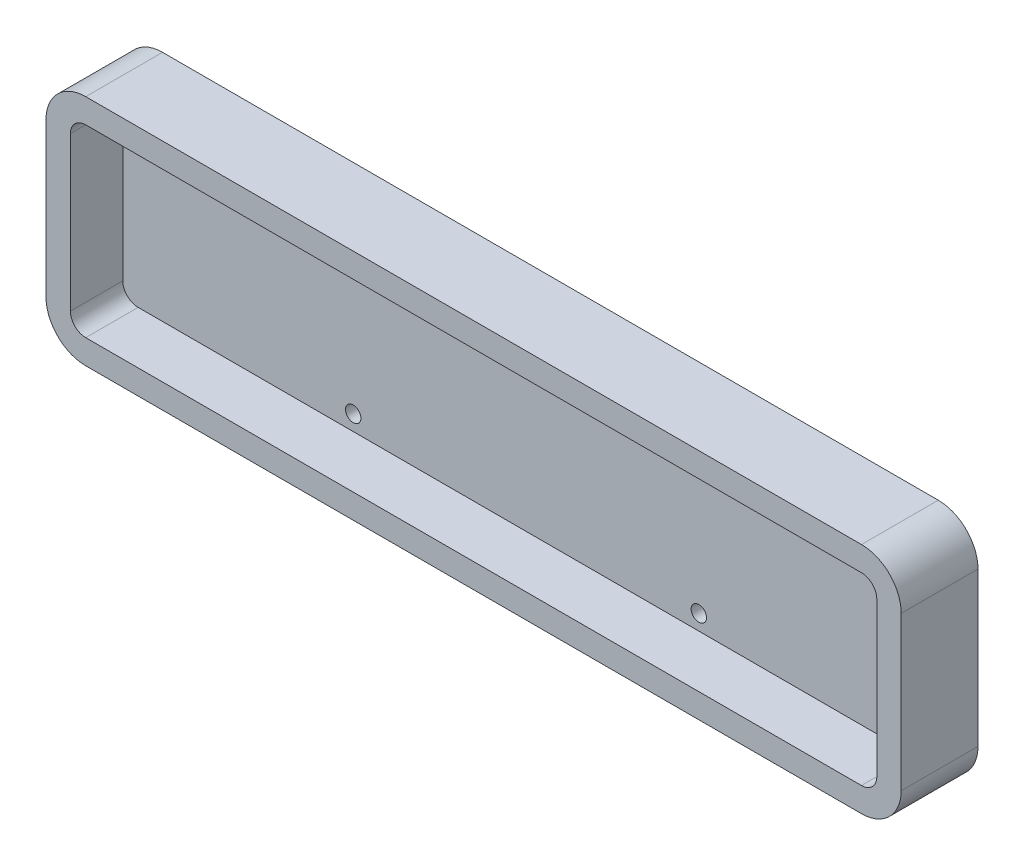
SolidWorks part; units mm, degrees
material "6061-T6 (SS)"
ref_plane "Front Plane" through (0, 0, 0) normal (0, 0, 1) x (1, 0, 0)
ref_plane "Top Plane" through (0, 0, 0) normal (0, 1, 0) x (1, 0, 0)
ref_plane "Right Plane" through (0, 0, 0) normal (1, 0, 0) x (0, 0, -1)
sketch "Sketch1" plane through (0, 0, 0) normal (0, 0, 1) x (1, 0, 0)
  line L0 (-50.5, 15.175) -> (50.5, 15.175)
  line L1 (-50.5, -12) -> (50.5, -12)
  line L2 (-52.5, -10) -> (-52.5, 10)
  line L3 (-50.5, 12) -> (50.5, 12)
  line L4 (52.5, -10) -> (52.5, 10)
  line L5 (-52.5, -12) -> (52.5, 12) construction
  line L6 (-52.5, 12) -> (52.5, -12) construction
  line L7 (55.675, -10) -> (55.675, 10)
  line L8 (-50.5, -15.175) -> (50.5, -15.175)
  line L9 (-55.675, -10) -> (-55.675, 10)
  arc A0 (-52.5, -10) -> (-50.5, -12) centre (-50.5, -10) ccw
  arc A1 (50.5, -12) -> (52.5, -10) centre (50.5, -10) ccw
  arc A2 (52.5, 10) -> (50.5, 12) centre (50.5, 10) ccw
  arc A3 (-50.5, 12) -> (-52.5, 10) centre (-50.5, 10) ccw
  arc A4 (55.675, 10) -> (50.5, 15.175) centre (50.5, 10) ccw
  arc A5 (50.5, -15.175) -> (55.675, -10) centre (50.5, -10) ccw
  arc A6 (-55.675, -10) -> (-50.5, -15.175) centre (-50.5, -10) ccw
  arc A7 (-50.5, 15.175) -> (-55.675, 10) centre (-50.5, 10) ccw
  point P0 (0, 0)
  dimension "D3" = 2
  dimension "D1" = 105
  dimension "D2" = 24
  dimension "D4" = 3.175
extrude "Boss-Extrude1" add sketch "Sketch1" along normal blind 10
extrude "Boss-Extrude2" add sketch "Sketch1<2>" along normal blind 3.175 contours L3 A3 L2 A0 L1 A1 L4 A2 region at (0, 0, 0)
sketch "Sketch1<2>" plane through (0, 0, 0) normal (0, 0, 1) x (1, 0, 0) same geometry as "Sketch1"
sketch "Sketch2" plane through (0, 0, 0) normal (0, 0, -1) x (-1, 0, 0)
  line L0 (-70.1691, 0) -> (70.1691, 0) construction
  line L1 (-22.5, -10) -> (22.5, -10) construction
  line L2 (-22.5, -10) -> (-22.5, 10) construction
  line L3 (-22.5, 10) -> (22.5, 10) construction
  line L4 (22.5, -10) -> (22.5, 10) construction
  line L5 (-22.5, -10) -> (22.5, 10) construction
  line L6 (-22.5, 10) -> (22.5, -10) construction
  line L7 (0, -26.7001) -> (0, 26.7001) construction
  circle A0 centre (22.5, 10) radius 1
  circle A1 centre (22.5, -10) radius 1
  circle A2 centre (-22.5, -10) radius 1
  circle A3 centre (-22.5, 10) radius 1
  point P0 (0, 0)
  point P10 (0, 0)
  point P13 (0, 0)
  dimension "D3" = 2
  dimension "D1" = 45
  dimension "D2" = 20
extrude "Cut-Extrude1" cut sketch "Sketch2" against normal up to surface (3.175 mm away) up to face at (0, 0, 3.175)
